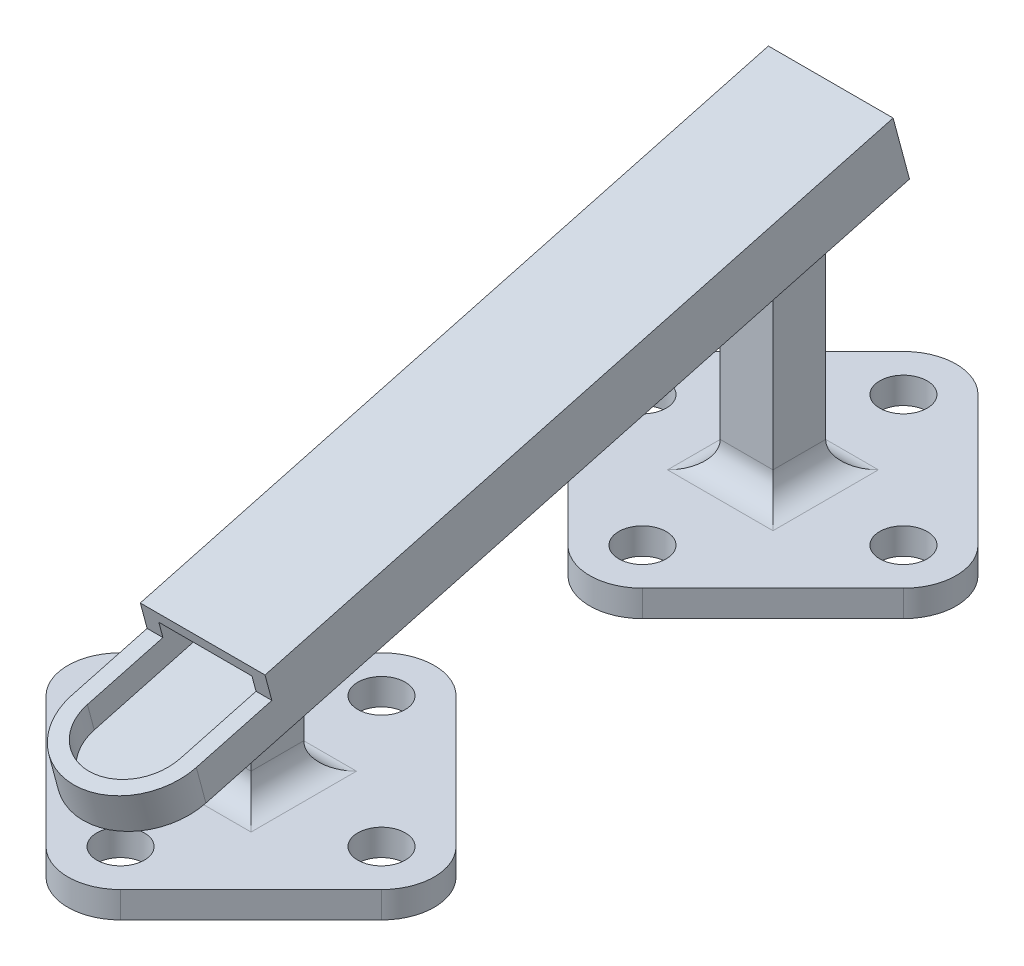
SolidWorks part; units mm, degrees
ref_plane "Front" through (0, 0, 0) normal (0, 0, 1) x (1, 0, 0)
ref_plane "Top" through (0, 0, 0) normal (0, 1, 0) x (1, 0, 0)
ref_plane "Right" through (0, 0, 0) normal (1, 0, 0) x (0, 0, -1)
ref_axis "Axis1" through (0, 55, 0) along (0, -1, 0)
ref_axis "Axis2" through (88.99, 0, 0) along (-1, 0, 0)
ref_axis "Axis3" through (0, 0, 55) along (0, 0, -1)
sketch "Sketch1" plane through (0, 0, 0) normal (0, 1, 0) x (1, 0, 0)
  line L0 (-24.75, 0) -> (0, 24.75) construction
  line L9 (-24.75, 0) -> (0, -24.75) construction
  line L11 (0, 24.75) -> (24.75, 0) construction
  line L12 (0, -24.75) -> (24.75, 0) construction
  line L13 (-24.75, 0) -> (24.75, 0) construction
  line L14 (0, 24.75) -> (0, -24.75) construction
  line L15 (-31.8211, 7.0711) -> (-7.0711, 31.8211)
  line L16 (7.0711, 31.8211) -> (31.8211, 7.0711)
  line L17 (7.0711, -31.8211) -> (31.8211, -7.0711)
  line L18 (-31.8211, -7.0711) -> (-7.0711, -31.8211)
  line L19 (0, -38.8921) -> (38.8921, 0) construction
  line L20 (-38.8921, 0) -> (0, -38.8921) construction
  line L21 (0, 38.8921) -> (38.8921, 0) construction
  line L22 (-38.8921, 0) -> (0, 38.8921) construction
  arc A4 (7.0711, -31.8211) -> (-7.0711, -31.8211) centre (0, -24.75) cw
  arc A5 (31.8211, 7.0711) -> (31.8211, -7.0711) centre (24.75, 0) cw
  arc A6 (-7.0711, 31.8211) -> (7.0711, 31.8211) centre (0, 24.75) cw
  arc A7 (-31.8211, 7.0711) -> (-31.8211, -7.0711) centre (-24.75, 0) ccw
  circle A8 centre (0, 24.75) radius 4.5
  circle A9 centre (24.75, 0) radius 4.5
  circle A10 centre (0, -24.75) radius 4.5
  circle A11 centre (-24.75, 0) radius 4.5
  point P1 (0, 0)
  dimension "D3" = 10
  dimension "D4" = 9
  dimension "D1" = 49.5
  dimension "D2" = 10
extrude "Boss-Extrude1" add sketch "Sketch1" along normal mid plane 5
ref_plane "Plane1" through (0, 0, 49.5) normal (0, 0, 1) x (1, 0, 0)
mirror "Mirror3" about plane through (0, 0, 49.5) normal (0, 0, 1) of bodies 101
sketch "Sketch2" plane through (0, 0, 0) normal (1, 0, 0) x (0, 0, -1)
  line L0 (-106.0711, 2.5) -> (-130.8211, 2.5) construction
  line L1 (-104, 2.5) -> (-94, 2.5)
  line L2 (-104, 2.5) -> (-104, 47.5)
  line L3 (-104, 47.5) -> (-94, 47.5)
  line L4 (-94, 2.5) -> (-94, 47.5)
  line L5 (-106.0711, -2.5) -> (-91.9289, -2.5) construction
  line L6 (-67.1789, -2.5) -> (-91.9289, -2.5) construction
  point P8 (-99, -2.5)
  point P9 (-99, 47.5)
  dimension "D1" = 10
  dimension "D2" = 50
extrude "Boss-Extrude2" add sketch "Sketch2" along normal mid plane 10 separate body
mirror "Mirror5" about plane through (0, 0, 49.5) normal (0, 0, 1) of bodies 103
sketch "Sketch3" plane through (0, 0, 0) normal (1, 0, 0) x (0, 0, -1)
  line L0 (-104, 17.5) -> (5, 46.7065)
  line L1 (-67.1789, -2.5) -> (-91.9289, -2.5) construction
  line L2 (-104, 47.5) -> (-104, 2.5) construction
  line L3 (-106.0711, 2.5) -> (-130.8211, 2.5) construction
  line L4 (5, 47.5) -> (5, 2.5) construction
  point P6 (-104, 17.5)
  dimension "D1" = 15
  dimension "D2" = 15
extrude "Cut-Extrude1" cut sketch "Sketch3" against normal through all both and the other way through all
sketch "Sketch4" plane through (0, 0, 0) normal (1, 0, 0) x (0, 0, -1)
  line L0 (-130.8211, 10.3133) -> (14.0678, 49.1362)
  line L1 (-130.8211, 10.3133) -> (-131.3387, 12.2452)
  line L2 (14.0678, 49.1362) -> (13.5502, 51.068)
  line L3 (-131.3387, 12.2452) -> (13.5502, 51.068)
  line L6 (-104, 17.5) -> (-94, 20.1795) construction
  dimension "D1" = 2
  dimension "D2" = 150
extrude "Boss-Extrude3" add sketch "Sketch4" along normal mid plane 23.66 separate body
combine bodies "Combine1" operation type add bodies to combine 102 106
combine bodies "Combine2" operation type add bodies to combine 107 101
fillet "Fillet1" radius 5 4 edges at (0, 2.5, 94) (-5, 2.5, 99) (0, 2.5, 104) (5, 2.5, 99)
fillet "Fillet2" radius 5 4 edges at (0, 2.5, 5) (0, 2.5, -5) (-5, 2.5, 0) (5, 2.5, 0)
sketch "Sketch5" plane through (0, 44.2596, 11.8593) normal (0, 0.9659, 0.2588) x (1, 0, 0)
  line L0 (11.83, -111.8642) -> (0, -111.8642) construction
  line L1 (11.83, 26.3058) -> (11.83, -123.6942) construction
  line L2 (0, -111.8642) -> (0, -123.6942) construction
  line L3 (11.83, -123.6942) -> (-11.83, -123.6942) construction
  line L4 (-11.83, -111.8642) -> (-11.83, -123.6942)
  line L5 (-11.83, -123.6942) -> (0, -123.6942)
  line L6 (0, -123.6942) -> (11.83, -123.6942)
  line L7 (11.83, -123.6942) -> (11.83, -111.8642)
  circle A0 centre (0, -111.8642) radius 8.73 construction
  circle A1 centre (0, -111.8642) radius 8.83
  circle A2 centre (0, -111.8642) radius 11.83
  line M3 (-11.83, 26.3058) -> (-11.83, -123.6942)
  line M4 (-11.83, -123.6942) -> (11.83, -123.6942)
  line M5 (11.83, -123.6942) -> (11.83, 26.3058)
  dimension "D1" = 17.46
  dimension "D2" = 0.1
  dimension "D3" = 3
extrude "Cut-Extrude4" cut sketch "Sketch5" against normal up to next (2 mm away) contours A2 M3 M4 | A2 M4 M5 region at (-9.1876, 12.9291, 128.7863) region at (9.1876, 12.9291, 128.7863)
sketch "Sketch6" plane through (0, 44.2596, 11.8593) normal (0, 0.9659, 0.2588) x (1, 0, 0)
  line L6 (8.83, -111.8642) -> (8.83, 23.3058)
  line L7 (8.83, 23.3058) -> (-8.83, 23.3058)
  line L8 (-8.83, 23.3058) -> (-8.83, -111.8642)
  line L9 (8.83, -111.8642) -> (8.83, 23.3058)
  line L10 (8.83, 23.3058) -> (-8.83, 23.3058)
  line L11 (-8.83, 23.3058) -> (-8.83, -111.8642)
  line L12 (11.83, -111.8642) -> (11.83, 26.3058)
  line L13 (11.83, 26.3058) -> (-11.83, 26.3058)
  line L14 (-11.83, 26.3058) -> (-11.83, -111.8642)
  line L15 (11.83, -111.8642) -> (11.83, 26.3058)
  line L16 (11.83, 26.3058) -> (-11.83, 26.3058)
  line L17 (-11.83, 26.3058) -> (-11.83, -111.8642)
  arc A2 (-8.83, -111.8642) -> (8.83, -111.8642) centre (0, -111.8642) ccw
  arc A3 (-8.83, -111.8642) -> (8.83, -111.8642) centre (0, -111.8642) ccw
  arc A4 (-11.83, -111.8642) -> (11.83, -111.8642) centre (0, -111.8642) ccw
  arc A5 (-11.83, -111.8642) -> (11.83, -111.8642) centre (0, -111.8642) ccw
  dimension "D1" = 3
  dimension "D2" = 0
extrude "Boss-Extrude4" add sketch "Sketch6" along normal blind 5
sketch "Sketch7" plane through (0, 49.0892, 13.1534) normal (0, 0.9659, 0.2588) x (1, 0, 0)
  line L1 (-11.83, -97.0342) -> (-8.83, -97.0342)
  line L2 (-8.83, 23.3058) -> (-8.83, -111.8642) construction
  line L3 (11.83, -111.8642) -> (11.83, 26.3058)
  line L4 (11.83, 26.3058) -> (-11.83, 26.3058)
  line L5 (-11.83, 26.3058) -> (-11.83, -111.8642)
  line L6 (11.83, -97.0342) -> (11.83, 26.3058)
  line L7 (11.83, 26.3058) -> (-11.83, 26.3058)
  line L8 (-11.83, 26.3058) -> (-11.83, -97.0342)
  line L10 (8.83, -111.8642) -> (8.83, 23.3058) construction
  line L11 (8.83, -97.0342) -> (11.83, -97.0342)
  line L12 (8.83, 23.3058) -> (-8.83, 23.3058) construction
  line L13 (8.83, 23.3058) -> (-8.83, 23.3058)
  line L14 (-8.83, 23.3058) -> (-8.83, -97.0342)
  line L15 (8.83, -97.0342) -> (8.83, 23.3058)
  arc A1 (-11.83, -111.8642) -> (11.83, -111.8642) centre (0, -111.8642) ccw
  arc A4 (-8.83, -111.8642) -> (8.83, -111.8642) centre (0, -111.8642) ccw construction
  dimension "D2" = 6
  dimension "D1" = 0
extrude "Boss-Extrude5" add sketch "Sketch7" along normal blind 5
sketch "Sketch8" plane through (0, 0, 0) normal (1, 0, 0) x (0, 0, -1)
  line L0 (-108.1753, 28.8045) -> (-107.6577, 26.8727)
  line L1 (-108.1753, 28.8045) -> (-106.8812, 23.9749) construction
  line L2 (-107.6577, 26.8727) -> (11.4796, 58.7954)
  line L3 (14.0678, 49.1362) -> (10.962, 60.7273) construction
  line L4 (11.4796, 58.7954) -> (10.962, 60.7273)
  line L5 (10.962, 60.7273) -> (-108.1753, 28.8045)
  dimension "D1" = 2
extrude "Boss-Extrude6" add sketch "Sketch8" along normal up to next and the other way up to next
sketch "Sketch9" plane through (0, 6.032, -22.5117) normal (0, -0.2588, 0.9659) x (1, 0, 0)
  line L4 (8.83, 53.8209) -> (-8.83, 53.8209)
  line L5 (-8.83, 53.8209) -> (-8.83, 45.8209)
  line L6 (-8.83, 45.8209) -> (8.83, 45.8209)
  line L7 (8.83, 45.8209) -> (8.83, 53.8209)
  line L8 (8.83, 53.8209) -> (-8.83, 53.8209)
  line L9 (-8.83, 53.8209) -> (-8.83, 45.8209)
  line L10 (-8.83, 45.8209) -> (8.83, 45.8209)
  line L11 (8.83, 45.8209) -> (8.83, 53.8209)
  dimension "D1" = 0
extrude "Cut-Extrude5" cut sketch "Sketch9" against normal through all
